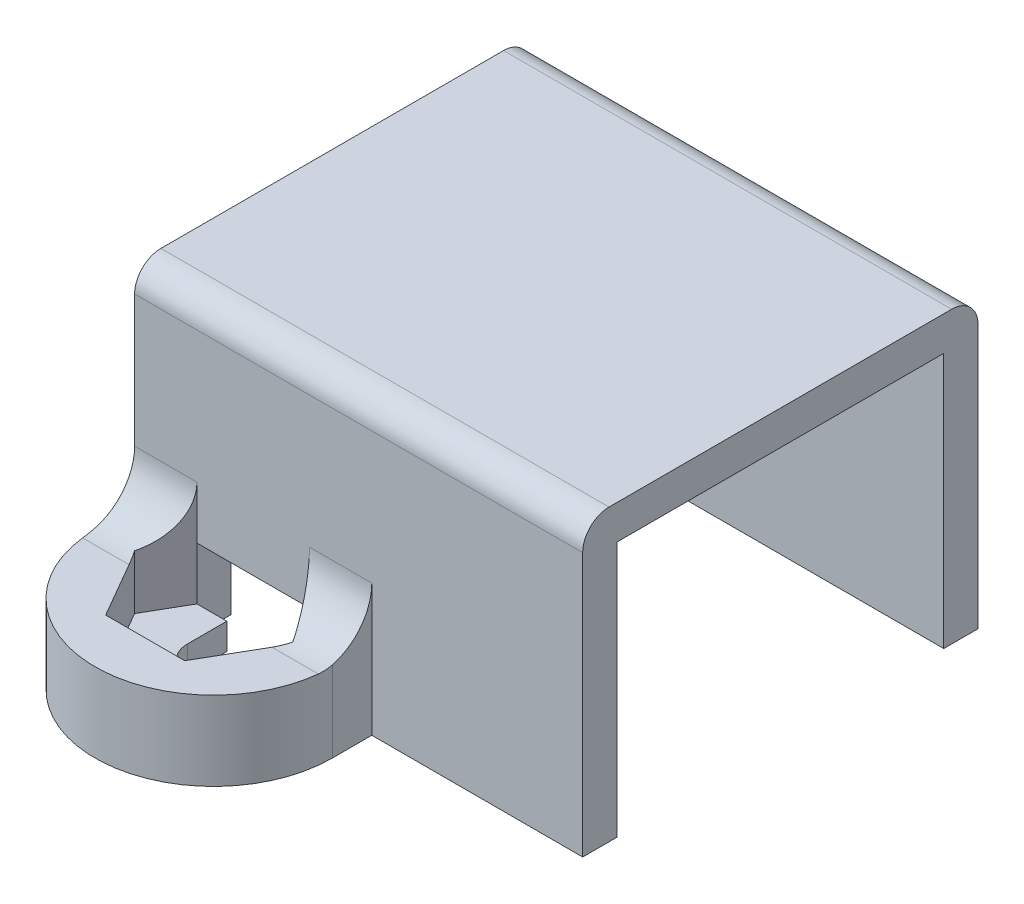
SolidWorks part; units mm, degrees
material "ABS"
ref_plane "Alzado" through (0, 0, 0) normal (0, 0, 1) x (1, 0, 0)
ref_plane "Planta" through (0, 0, 0) normal (0, 1, 0) x (1, 0, 0)
ref_plane "Vista lateral" through (0, 0, 0) normal (1, 0, 0) x (0, 0, -1)
sketch "Croquis1" plane through (0, 0, 0) normal (0, 1, 0) x (1, 0, 0)
  line L1 (-8.5, -13.5) -> (8.5, -13.5)
  line L2 (-8.5, -13.5) -> (-8.5, 13.5)
  line L3 (-8.5, 13.5) -> (8.5, 13.5)
  line L4 (8.5, -13.5) -> (8.5, 13.5)
  line L5 (-8.5, -13.5) -> (8.5, 13.5) construction
  line L6 (-8.5, 13.5) -> (8.5, -13.5) construction
  point P0 (0, 0)
  dimension "D1" = 17
  dimension "D2" = 27
extrude "Saliente-Extruir1" add sketch "Croquis1" along normal blind 11
sketch "Croquis2" plane through (0, 11, 0) normal (0, 1, 0) x (1, 0, 0)
  line L1 (-8.5, -7.5) -> (8.5, -7.5) construction
  line L2 (-8.5, 13.5) -> (-8.5, -13.5) construction
  line L3 (-8.5, 7.5) -> (8.5, 7.5) construction
  line L4 (-8.5, 13.5) -> (8.5, 13.5)
  line L5 (-8.5, 13.5) -> (-8.5, 7.5)
  line L6 (-8.5, 7.5) -> (8.5, 7.5)
  line L7 (8.5, 13.5) -> (8.5, 7.5)
  line L8 (-8.5, -7.5) -> (8.5, -7.5)
  line L9 (-8.5, -7.5) -> (-8.5, -13.5)
  line L10 (-8.5, -13.5) -> (8.5, -13.5)
  line L11 (8.5, -7.5) -> (8.5, -13.5)
  point P0 (0, 0)
  dimension "D1" = 6
  dimension "D2" = 6
extrude "Cortar-Extruir1" cut sketch "Croquis2" against normal blind 6
sketch "Croquis3" plane through (0, 0, 13.5) normal (0, 0, 1) x (1, 0, 0)
  line L0 (8.5, 5) -> (-8.5, 5) construction
  line L1 (8.5, 0) -> (0.5, 0)
  line L2 (8.5, 0) -> (8.5, 5)
  line L3 (8.5, 5) -> (0.5, 5)
  line L4 (0.5, 0) -> (0.5, 5)
  dimension "D1" = 8
extrude "Cortar-Extruir2" cut sketch "Croquis3" against normal blind 6
sketch "Croquis4" plane through (0, 0, -13.5) normal (0, 0, -1) x (-1, 0, 0)
  line L0 (8.5, 5) -> (-8.5, 5) construction
  line L1 (-8.5, 0) -> (-0.5, 0)
  line L2 (-8.5, 0) -> (-8.5, 5)
  line L3 (-8.5, 5) -> (-0.5, 5)
  line L4 (-0.5, 0) -> (-0.5, 5)
  dimension "D1" = 8
extrude "Cortar-Extruir3" cut sketch "Croquis4" against normal blind 6
sketch "Croquis5" plane through (0, 5, 0) normal (0, 1, 0) x (1, 0, 0)
  line L0 (-8.5, 9) -> (-8.5, 13.5)
  line L1 (0.5, 13.5) -> (-8.5, 13.5) construction
  line L2 (0.5, 7.5) -> (0.5, 13.5) construction
  line L3 (-8.5, 13.5) -> (-8.5, 7.5) construction
  line L4 (-8.5, 13.5) -> (0.5, 13.5)
  line L5 (0.5, 13.5) -> (0.5, 9)
  line L6 (-8.5, -9) -> (-8.5, -13.5)
  line L14 (-8.5, -13.5) -> (0.5, -13.5) construction
  line L15 (-8.5, -7.5) -> (-8.5, -13.5) construction
  line L16 (0.5, -7.5) -> (0.5, -13.5) construction
  line L17 (-8.5, -13.5) -> (0.5, -13.5)
  line L18 (0.5, -13.5) -> (0.5, -9)
  line L19 (0.5, -7.5) -> (-8.5, -7.5) construction
  arc A0 (-4, 13.5) -> (0.5, 9) centre (-4, 9) cw
  arc A1 (-8.5, 9) -> (-4, 13.5) centre (-4, 9) cw
  arc A2 (-4, -13.5) -> (-8.5, -9) centre (-4, -9) cw
  arc A3 (-4, -13.5) -> (0.5, -9) centre (-4, -9) ccw
  line M1 (0.5, 7.5) -> (0.5, 13.5)
  line M2 (0.5, 13.5) -> (-8.5, 13.5)
  line M3 (-8.5, 13.5) -> (-8.5, 7.5)
  dimension "D1" = 4.5
  dimension "D2" = 1.5
extrude "Cortar-Extruir8" cut sketch "Croquis5" against normal blind 6 contours A1 L4 M3 | A0 M2 M1 | L17 A2 L6 | A3 L17 L18 region at (-0.5052, 5, -12.4948) region at (-7.4948, 5, -12.4948) region at (-7.4948, 5, 12.4948) region at (-0.5052, 5, 12.4948)
sketch "Croquis7" plane through (0, 5, 0) normal (0, 1, 0) x (1, 0, 0)
  line L0 (-8.5, 7.5) -> (-8.5, 9)
  line L1 (-8.5, 7.5) -> (0.5, 7.5)
  line L2 (-8.5, 7.5) -> (8.5, 7.5) construction
  line L3 (-8.5, 7.5) -> (0.5, 7.5) construction
  line L4 (0.5, 7.5) -> (0.5, 9)
  line L5 (-8.5, -9) -> (-8.5, -7.5)
  line L7 (-8.5, -7.5) -> (0.5, -7.5)
  line L8 (0.5, -7.5) -> (0.5, -9)
  arc A0 (0.5, 9) -> (-8.5, 9) centre (-4, 9) ccw
  arc A1 (-8.5, -9) -> (0.5, -9) centre (-4, -9) ccw
  arc A2 (-8.5, -9) -> (0.5, -9) centre (-4, -9) ccw construction
  dimension "D1" = 4.5
extrude "Cortar-Extruir16" cut sketch "Croquis7" against normal blind 2
sketch "Croquis10" plane through (0, 3, 0) normal (0, 1, 0) x (1, 0, 0)
  line L0 (-6.134, 7.5) -> (-1.866, 7.5)
  line L1 (-8.5, 7.5) -> (0.5, 7.5) construction
  line L3 (-1, 9) -> (-2.5, 11.5981)
  line L4 (-2.5, 11.5981) -> (-5.5, 11.5981)
  line L5 (-5.5, 11.5981) -> (-7, 9)
  line L6 (-7, 9) -> (-6.134, 7.5)
  line L8 (-1.866, 7.5) -> (-1, 9)
  line L9 (-4, 6.4019) -> (-2.5, 6.4019) [skipped]
  arc A1 (-1.8787, 7.5) -> (-1.75, 7.701) centre (-4, 9) ccw construction
  arc A2 (-6.25, 7.701) -> (-6.1213, 7.5) centre (-4, 9) ccw construction
  dimension "D1" = 3
  dimension "D2" = 1.5
extrude "Cortar-Extruir17" cut sketch "Croquis10" against normal blind 2
sketch "Croquis11" plane through (0, 3, 0) normal (0, 1, 0) x (1, 0, 0)
  line L1 (0.5, -7.5) -> (-8.5, -7.5) construction
  line L2 (-6.134, -7.5) -> (-1.866, -7.5)
  line L3 (-1, -9) -> (-1.866, -7.5)
  line L5 (-6.134, -7.5) -> (-7, -9)
  line L6 (-7, -9) -> (-5.5, -11.5981)
  line L7 (-5.5, -11.5981) -> (-2.5, -11.5981)
  line L8 (-2.5, -11.5981) -> (-1, -9)
  line L9 (8.5, -7.5) -> (-8.5, -7.5) construction
  line L11 (-2.5, -6.4019) -> (-4, -6.4019) [skipped]
  arc A0 (-1.75, -7.701) -> (-1.8787, -7.5) centre (-4, -9) ccw construction
  arc A1 (-6.1213, -7.5) -> (-6.25, -7.701) centre (-4, -9) ccw construction
extrude "Cortar-Extruir18" cut sketch "Croquis11" against normal blind 2
fillet "Redondeo5" radius 2 4 edges at (-0.683, 3, 7.5) (-7.317, 3, 7.5) (-0.683, 3, -7.5) (-7.317, 3, -7.5)
sketch "Croquis12" plane through (-8.5, 0, 0) normal (-1, 0, 0) x (0, 0, 1)
  line L0 (-6.2, 0) -> (6.2, 0)
  line L1 (-9, 0) -> (9, 0) construction
  line L5 (-6.2, 0) -> (-6.2, 7.7)
  line L7 (6.2, 0) -> (6.2, 7.7)
  line L10 (-4.2, 9.7) -> (4.2, 9.7)
  arc A0 (-4.2, 9.7) -> (-6.2, 7.7) centre (-4.2, 7.7) ccw
  arc A1 (6.2, 7.7) -> (4.2, 9.7) centre (4.2, 7.7) ccw
  dimension "D1" = 2
  dimension "D2" = 8.4
extrude "Cortar-Extruir19" cut sketch "Croquis12" against normal blind 17
sketch "Croquis13" plane through (8.5, 0, 0) normal (1, 0, 0) x (0, 0, -1)
  line L0 (-6.2, 7.7) -> (-6.2, 9.7)
  line L1 (-6.2, 9.7) -> (-4.2, 9.7)
  line L2 (6.2, 7.7) -> (6.2, 9.7)
  line L3 (6.2, 9.7) -> (4.2, 9.7)
  arc A0 (-4.2, 9.7) -> (-6.2, 7.7) centre (-4.2, 7.7) ccw
  arc A1 (6.2, 7.7) -> (4.2, 9.7) centre (4.2, 7.7) ccw construction
  arc A2 (6.2, 7.7) -> (4.2, 9.7) centre (4.2, 7.7) ccw
extrude "Cortar-Extruir20" cut sketch "Croquis13" against normal blind 10
fillet "Redondeo6" radius 1 2 edges at (0, 11, -7.5) (0, 11, 7.5)
sketch "Croquis14" plane through (0, 1, 0) normal (0, 1, 0) x (1, 0, 0)
  line L0 (-5, 9) -> (-5, 7.5)
  line L1 (-8.5, 7.5) -> (8.5, 7.5) construction
  line L2 (-3, 9) -> (-3, 7.5)
  line L3 (-6.134, 7.5) -> (-1.866, 7.5) construction
  line L4 (-3, 7.5) -> (-5, 7.5)
  arc A1 (-3, 9) -> (-5, 9) centre (-4, 9) ccw
extrude "Cortar-Extruir21" cut sketch "Croquis14" against normal blind 1 contours A1 L0 L4 L2
sketch "Croquis15" plane through (0, 1, 0) normal (0, 1, 0) x (1, 0, 0)
  line L0 (-5, -9) -> (-5, -7.5)
  line L1 (-1.866, -7.5) -> (-6.134, -7.5) construction
  line L2 (-5, -7.5) -> (-3, -7.5)
  line L3 (-3, -7.5) -> (-3, -9)
  arc A1 (-5, -9) -> (-3, -9) centre (-4, -9) ccw
extrude "Cortar-Extruir22" cut sketch "Croquis15" against normal blind 1
sketch "Croquis16" plane through (0, 0, -7.5) normal (0, 0, -1) x (-1, 0, 0)
  line L0 (1.866, 3) -> (6.134, 3)
  line L1 (1.866, 1) -> (1.866, 5) construction
  line L2 (6.134, 1) -> (6.134, 5) construction
  line L3 (6.134, 3) -> (6.134, 1)
  line L4 (6.134, 1) -> (5, 1)
  line L7 (3, 1) -> (1.866, 1)
  line L8 (1.866, 1) -> (1.866, 3)
  line L9 (3, 1) -> (5, 1)
extrude "Cortar-Extruir26" cut sketch "Croquis16" against normal blind 1.3 contours L0 L3 L4 L9 L7 L8
sketch "Croquis17" plane through (0, 0, 7.5) normal (0, 0, 1) x (1, 0, 0)
  line L0 (-6.134, 3) -> (-1.866, 3)
  line L1 (-6.134, 1) -> (-6.134, 5) construction
  line L2 (-1.866, 1) -> (-1.866, 5) construction
  line L3 (-1.866, 3) -> (-1.866, 1)
  line L4 (-1.866, 1) -> (-6.134, 1)
  line L5 (-6.134, 1) -> (-6.134, 3)
extrude "Cortar-Extruir27" cut sketch "Croquis17" against normal blind 1.3
sketch "Croquis19" plane through (0, 0, 6.2) normal (0, 0, -1) x (-1, 0, 0)
  line L0 (1.866, 1) -> (1.866, 0)
  line L1 (-8.5, 0) -> (8.5, 0) construction
  line L2 (1.866, 0) -> (6.134, 0)
  line L3 (6.134, 0) -> (6.134, 1)
  line L4 (6.134, 1) -> (1.866, 1)
extrude "Cortar-Extruir28" cut sketch "Croquis19" against normal blind 1.3
sketch "Croquis20" plane through (0, 0, -6.2) normal (0, 0, 1) x (1, 0, 0)
  line L0 (-6.134, 1) -> (-1.866, 1)
  line L1 (-1.866, 1) -> (-1.866, 0)
  line L2 (8.5, 0) -> (-8.5, 0) construction
  line L3 (-1.866, 0) -> (-6.134, 0)
  line L4 (-6.134, 0) -> (-6.134, 1)
extrude "Cortar-Extruir29" cut sketch "Croquis20" against normal blind 1.3
sketch "Sketch1" plane through (0, 11, 0) normal (0, 1, 0) x (1, 0, 0)
  line L0 (-8.5, 0) -> (8.5, 0) construction
  line L1 (-8.5, 6.5) -> (-8.5, -6.5) construction
  line L2 (8.5, -6.5) -> (8.5, 6.5) construction
